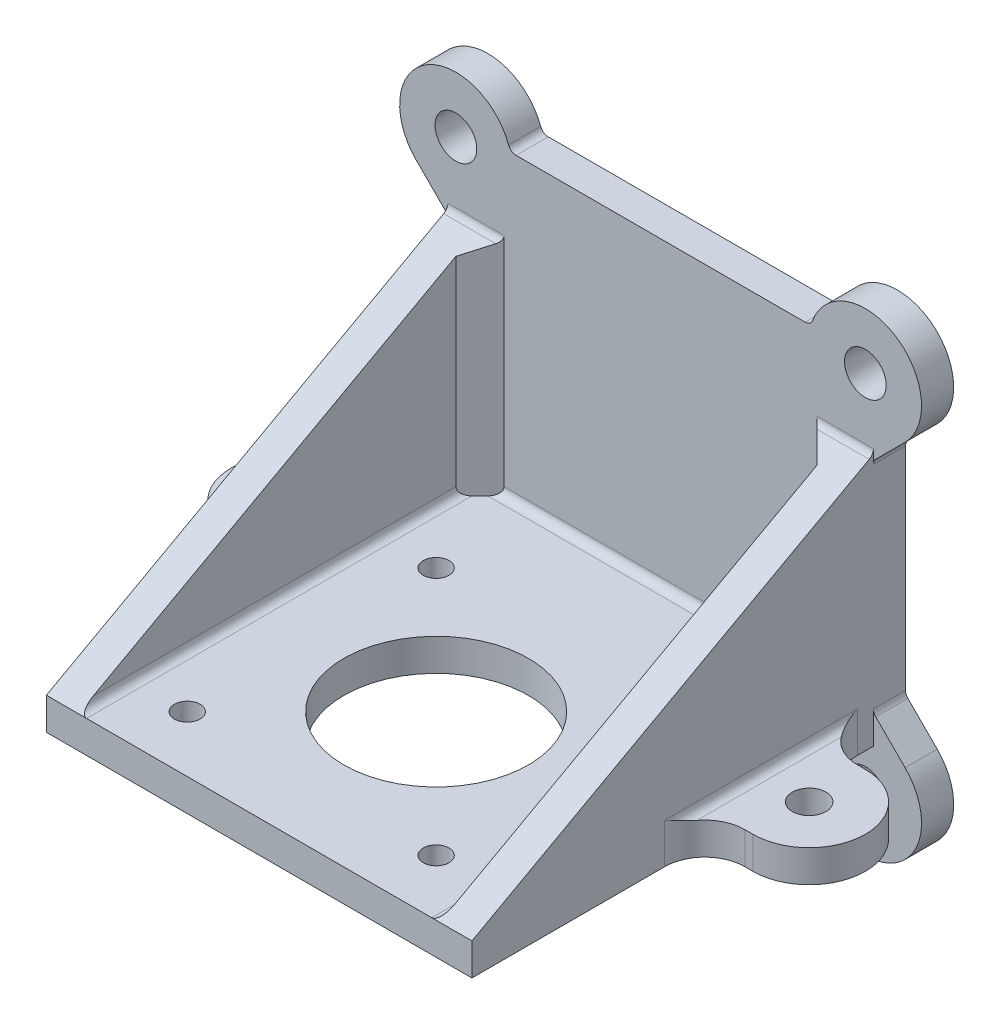
SolidWorks part; units mm, degrees
ref_plane "Plan de face" through (0, 0, 0) normal (0, 0, 1) x (1, 0, 0)
ref_plane "Plan de dessus" through (0, 0, 0) normal (0, 1, 0) x (1, 0, 0)
ref_plane "Plan de droite" through (0, 0, 0) normal (1, 0, 0) x (0, 0, -1)
sketch "Esquisse1" plane through (0, 0, 0) normal (0, 0, 1) x (1, 0, 0)
  line L0 (48.9134, -5.2929) -> (-2.0866, -5.2929) construction
  line L1 (0.9134, -3.5147) -> (45.9134, -3.5147)
  line L2 (0.9134, -3.5147) -> (0.9134, 41.4853)
  line L3 (0.9134, 41.4853) -> (45.9134, 41.4853)
  line L4 (45.9134, -3.5147) -> (45.9134, 41.4853)
  line L6 (41.9134, -5.2929) -> (41.9134, -3.5147)
  line L7 (45.1353, -11.4142) -> (37.2358, -3.5147)
  line L10 (55.0348, -1.5147) -> (45.9134, 7.6066)
  line L13 (48.9134, 39.7071) -> (48.9134, -5.2929) construction
  line L17 (55.0348, 35.9289) -> (45.9134, 26.8076)
  circle A1 centre (48.9134, -5.2929) radius 2.6
  circle A3 centre (48.9134, -5.2929) radius 7
  circle A5 centre (48.9134, 39.7071) radius 2.6
  circle A7 centre (48.9134, 39.7071) radius 7
  point P4 (0, 0)
  point P9 (23.4134, -3.5147)
  point P10 (23.4134, -5.2929)
  point P23 (54.2063, -3.5147)
  dimension "D4" = 45
  dimension "D5" = 5.2
  dimension "D7" = 45
  dimension "D8" = 14
  dimension "D11" = 5.2
  dimension "D12" = 25.5
  dimension "D15" = 14
  dimension "D1" = 45
  dimension "D2" = 45
  dimension "D3" = 7
  dimension "D6" = 7
  dimension "D9" = 45
  dimension "D10" = 7
  dimension "D17" = 45
extrude "Boss.-Extru.1" add sketch "Esquisse1" along normal blind 4 contours A7 L3 L2 L1 A3 L4 | A3 L4 L1 A1 | A3 L10 L4 | A3 L6 L1 L7 | L4 A3 L1 | A3 L1 L6 | L4 A7 A5 | A7 L4 L17 | L3 A7 L4 | A7 L3 region at (23.0329, 18.8598, 0) region at (40.5283, -5.3327, 0) region at (41.9821, -3.9578, 0) region at (42.6292, -7.8959, 0) region at (49.7848, 46.4547, 0) region at (44.1787, 38.1472, 0) region at (44.4635, -1.784, 0) region at (48.0448, 30.9473, 0) region at (48.0448, 3.4669, 0)
ref_plane "Plan1" through (23.4134, 0, 0) normal (1, 0, 0) x (0, 0, -1)
mirror "Symétrie3" about plane through (23.4134, 0, 0) normal (1, 0, 0) of "Boss.-Extru.1"
sketch "Esquisse2" plane through (0, 0, 4) normal (0, 0, 1) x (1, 0, 0)
  line L1 (0, 0) -> (45.9134, 0)
  line L2 (0, 0) -> (0, 4)
  line L3 (0, 4) -> (45.9134, 4)
  line L4 (45.9134, 0) -> (45.9134, 4)
  line L7 (45.9134, 7.6066) -> (45.9134, 26.8076) construction
  dimension "D1" = 4
extrude "Boss.-Extru.2" add sketch "Esquisse2" along normal blind 50
sketch "Esquisse3" plane through (0, 4, 0) normal (0, 1, 0) x (1, 0, 0)
  line L0 (0, -54) -> (45.9134, -54) construction
  line L2 (45.9134, -4) -> (0, -4) construction
  line L3 (45.9134, -54) -> (0, -54) construction
  circle A0 centre (22.9567, -31.5) radius 11.5
  circle A1 centre (38.4567, -16) radius 1.6
  circle A2 centre (7.4567, -16) radius 1.6
  circle A3 centre (7.4567, -47) radius 1.6
  circle A4 centre (38.4567, -47) radius 1.6
  point P16 (22.9567, -54)
  dimension "D7" = 3.2
  dimension "D8" = 3.2
  dimension "D9" = 23
  dimension "D10" = 3.2
  dimension "D11" = 3.2
  dimension "D1" = 31
  dimension "D2" = 31
  dimension "D3" = 31
  dimension "D4" = 31
  dimension "D5" = 31
  dimension "D6" = 15.5
  dimension "D12" = 15.5
  dimension "D13" = 15.5
  dimension "D14" = 27.5
  dimension "D15" = 0
  dimension "D16" = 12
  dimension "D17" = 22.5
extrude "Enlèv. mat.-Extru.1" cut sketch "Esquisse3" against normal blind 97
sketch "Esquisse5" plane through (0, 0, 0) normal (0, -1, 0) x (1, 0, 0)
  line L0 (55.9134, 11) -> (45.9134, 11)
  line L2 (0, 4) -> (45.9134, 4) construction
  line L6 (55.9134, 25) -> (45.9134, 25)
  line L7 (45.9134, 54) -> (45.9134, 4) construction
  circle A0 centre (55.9134, 18) radius 2.1
  circle A1 centre (55.9134, 18) radius 7
  line M20 (45.9134, 4) -> (45.9134, 54)
  dimension "D1" = 4.2
  dimension "D2" = 14
  dimension "D3" = 14
  dimension "D4" = 10
extrude "Boss.-Extru.3" add sketch "Esquisse5" against normal up to surface (4 mm away) contours A1 L6 M20 | A1 A0 region at (48.4356, 0, 18) region at (49.1114, 0, 18) up to face at (38.4567, 4, 17.6)
mirror "Symétrie1" about plane through (23.4134, 0, 0) normal (1, 0, 0) of "Boss.-Extru.3"
sketch "Esquisse6" plane through (0.9134, 0, 0) normal (-1, 0, 0) x (0, 0, 1)
  line L0 (54, 4) -> (4, 31.4853)
  line L1 (4, 41.4853) -> (0, 41.4853) construction
  line L3 (54, 4) -> (54, 0) construction
  line L5 (54, 4) -> (54, 0)
  line L7 (54, 0) -> (0, 0)
  line L8 (0, 0) -> (0, 41.4853)
  line L9 (0, 41.4853) -> (4, 41.4853)
  line L10 (0, 26.8076) -> (4, 26.8076)
  line L11 (0, 31.4853) -> (4, 31.4853)
  line M22 (0, 26.8076) -> (0, 7.6066)
  line M23 (4, 7.6066) -> (4, 26.8076)
  line M24 (4, 26.8076) -> (0, 26.8076)
  line M25 (0, 7.6066) -> (4, 7.6066)
  dimension "D1" = 10
extrude "Boss.-Extru.4" add sketch "Esquisse6" along normal blind 4 contours M25 M23 M24 M22 | L11 L8 L7 L5 L0 M24 M23 M25 region at (0.9134, 10.7928, 21.4671) region at (0.9134, 17.2071, 2)
mirror "Symétrie2" about plane through (23.4134, 0, 0) normal (1, 0, 0) of "Boss.-Extru.4"
fillet "Congé3" radius 5 4 edges at (49.9134, 2, 25) (-3.0866, 2, 25) (49.9134, 2, 11) (-3.0866, 2, 11)
fillet "Congé4" radius 1 13 edges at (9.5911, -3.5147, 2) (37.2358, -3.5147, 2) (4.6838, 41.4853, 2) (42.1431, 41.4853, 2) (49.9134, 3.6066, 2) (-3.0866, 3.6066, 2) (47.9134, 31.4853, 4) (-1.0866, 31.4853, 4) (45.9134, 4, 29) (23.4134, 4, 4) (0.9134, 4, 29) (49.9134, 30.8076, 2) (-3.0866, 30.8076, 2)
fillet "Congé7" radius 1 2 edges at (49.9134, 4, 18) (-3.0866, 4, 18)
chamfer "Chanfrein1" distance 3 angle 45 3 edges at (0.9134, 18.5384, 4) (45.9134, 18.5384, 4) (23.4134, 0, 4)
sketch "Esquisse7" plane through (0, 0, 4) normal (0, 0, 1) x (1, 0, 0)
  line L0 (-3.0866, 0) -> (49.9134, 0) construction
  circle A0 centre (-2.0866, -5.2929) radius 5.2929
  circle A1 centre (48.9134, -5.2929) radius 5.2929
extrude "Enlèv. mat.-Extru.2" cut sketch "Esquisse7" along normal blind 6
sketch "Esquisse8" plane through (0, 0, 4) normal (0, 0, 1) x (1, 0, 0)
  line L0 (-2.0866, 0) -> (48.9134, 0) construction
  line L1 (-2.0866, -2) -> (-4.0866, -2)
  line L2 (-2.0866, -2) -> (-2.0866, 0)
  line L3 (-2.0866, 0) -> (-4.0866, 0)
  line L4 (-4.0866, -2) -> (-4.0866, 0)
  dimension "D1" = 2
  dimension "D2" = 2
extrude "Enlèv. mat.-Extru.3" cut sketch "Esquisse8" along normal blind 4.9901
mirror "Symétrie4" about plane through (23.4134, 0, 0) normal (1, 0, 0) of "Enlèv. mat.-Extru.3"
equation "\"0.5R\"=3"
